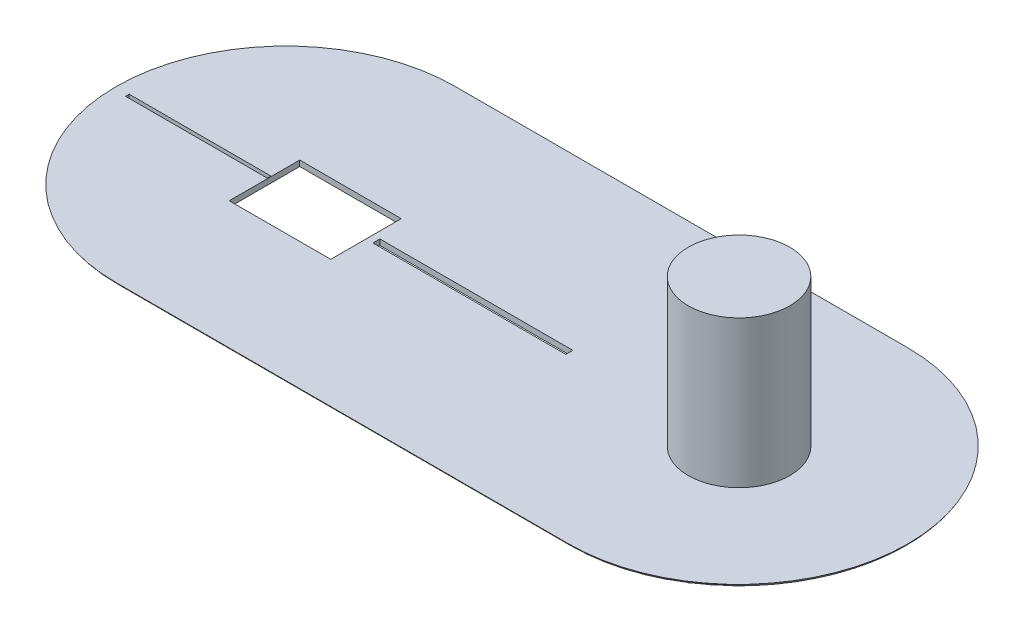
SolidWorks part; units mm, degrees
ref_plane "Front Plane" through (0, 0, 0) normal (0, 0, 1) x (1, 0, 0)
ref_plane "Top Plane" through (0, 0, 0) normal (0, 1, 0) x (1, 0, 0)
ref_plane "Right Plane" through (0, 0, 0) normal (1, 0, 0) x (0, 0, -1)
sketch "Sketch2" plane through (0, 0, 0) normal (0, 1, 0) x (1, 0, 0)
  line L0 (-42.314, 0) -> (59.286, 0) construction
  line L1 (-42.314, 38.1) -> (59.286, 38.1)
  line L2 (-42.314, -38.1) -> (59.286, -38.1)
  arc A0 (-42.314, 38.1) -> (-42.314, -38.1) centre (-42.314, 0) ccw
  arc A1 (59.286, -38.1) -> (59.286, 38.1) centre (59.286, 0) ccw
  point P3 (8.486, 0)
  dimension "D1" = 101.6
  dimension "D2" = 76.2
extrude "Boss-Extrude4" add sketch "Sketch2" along normal blind 1.27 contours L2 A1 L1 A0
sketch "Sketch11" plane through (0, 1.27, 0) normal (0, 1, 0) x (1, 0, 0)
  circle A0 centre (59.4609, 0) radius 11.403
extrude "Boss-Extrude6" add sketch "Sketch11" along normal blind 33.02
sketch "Sketch12" plane through (0, 1.27, 0) normal (0, 1, 0) x (1, 0, 0)
  line L1 (-45.5191, -9.4835) -> (-22.7265, -9.4835)
  line L2 (-45.5191, -9.4835) -> (-45.5191, 6.3447)
  line L3 (-45.5191, 6.3447) -> (-22.7265, 6.3447)
  line L4 (-22.7265, -9.4835) -> (-22.7265, 6.3447)
extrude "Cut-Extrude4" cut sketch "Sketch12" against normal blind 12.7
fillet "Fillet1" radius 2.54 4 edges at (-80.414, 0, 0) (8.486, 0, 38.1) (97.386, 0, 0) (8.486, 0, -38.1)
sketch "Sketch13" plane through (0, 0, 0) normal (0, -1, 0) x (1, 0, 0)
  line L1 (-77.4616, 0) -> (-45.6306, 0)
  line L2 (-77.4616, 0) -> (-77.4616, 0.8112)
  line L3 (-77.4616, 0.8112) -> (-45.6306, 0.8112)
  line L4 (-45.6306, 0) -> (-45.6306, 0.8112)
  line L5 (-21.1665, 0) -> (22.1438, 0)
  line L6 (-21.1665, 0) -> (-21.1665, 1.5694)
  line L7 (-21.1665, 1.5694) -> (22.1438, 1.5694)
  line L8 (22.1438, 0) -> (22.1438, 1.5694)
extrude "Cut-Extrude5" cut sketch "Sketch13" against normal blind 22.86
sketch "Sketch14" plane through (0, 0, 0) normal (0, -1, 0) x (1, 0, 0)
  text T0 "logi" font "Century Gothic" height in points 28
